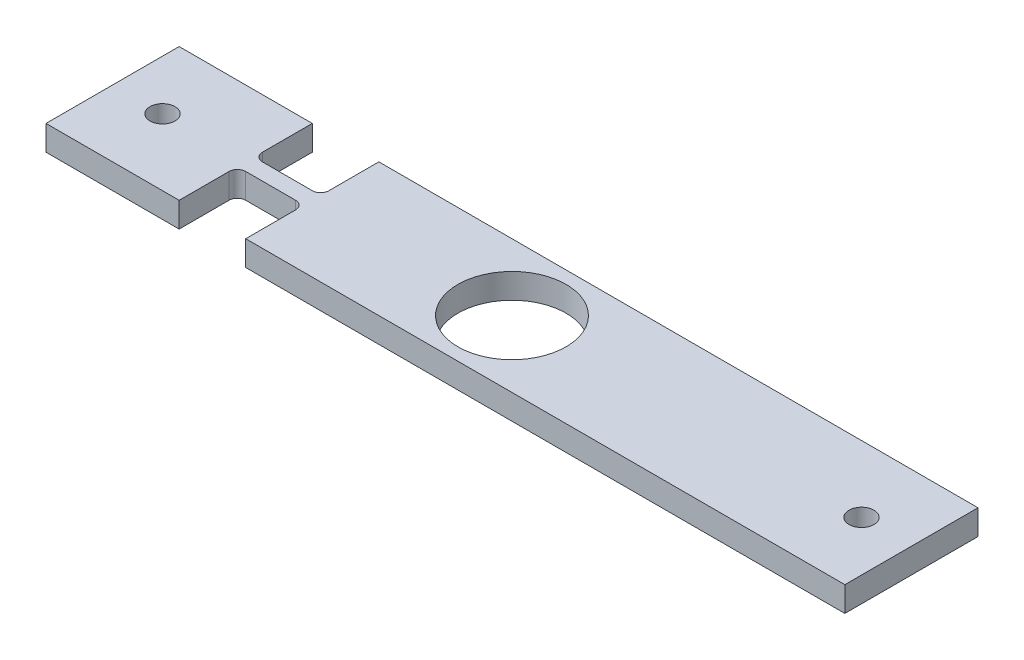
SolidWorks part; units mm, degrees
material "6061-T6 (SS)"
ref_plane "Front Plane" through (0, 0, 0) normal (0, 0, 1) x (1, 0, 0)
ref_plane "Top Plane" through (0, 0, 0) normal (0, 1, 0) x (1, 0, 0)
ref_plane "Right Plane" through (0, 0, 0) normal (1, 0, 0) x (0, 0, -1)
sketch "Sketch1" plane through (0, 0, 0) normal (0, 1, 0) x (1, 0, 0)
  line L1 (-152.4, 25.4) -> (152.4, 25.4)
  line L2 (-152.4, 25.4) -> (-152.4, -25.4)
  line L3 (-152.4, -25.4) -> (152.4, -25.4)
  line L4 (152.4, 25.4) -> (152.4, -25.4)
  line L5 (-152.4, 25.4) -> (152.4, -25.4) construction
  line L6 (-152.4, -25.4) -> (152.4, 25.4) construction
  point P0 (0, 0)
  dimension "D1" = 50.8
  dimension "D2" = 304.8
extrude "Boss-Extrude1" add sketch "Sketch1" along normal blind 9.525
sketch "Sketch2" plane through (0, 9.525, 0) normal (0, 1, 0) x (1, 0, 0)
  circle A0 centre (0, 0) radius 20.6375
  dimension "D1" = 41.275
extrude "Cut-Extrude1" cut sketch "Sketch2" against normal through all
sketch "Sketch3" plane through (0, 9.525, 0) normal (0, 1, 0) x (1, 0, 0)
  line L0 (152.4, -25.4) -> (152.4, 25.4) construction
  circle A0 centre (133.35, 0) radius 4.7625
  point P4 (0, 0)
  dimension "D1" = 9.525
  dimension "D2" = 19.05
extrude "Cut-Extrude2" cut sketch "Sketch3" against normal through all
sketch "Sketch4" plane through (0, 9.525, 0) normal (0, 1, 0) x (1, 0, 0)
  line L0 (152.4, 25.4) -> (-152.4, 25.4) construction
  line L1 (-101.6, 25.4) -> (-76.2, 25.4)
  line L2 (-101.6, 25.4) -> (-101.6, 6.35)
  line L3 (-98.425, 3.175) -> (-79.375, 3.175)
  line L4 (-76.2, 25.4) -> (-76.2, 6.35)
  line L5 (-101.6, -25.4) -> (-76.2, -25.4)
  line L6 (-101.6, -25.4) -> (-101.6, -6.35)
  line L7 (-98.425, -3.175) -> (-79.375, -3.175)
  line L8 (-76.2, -25.4) -> (-76.2, -6.35)
  line L9 (-152.4, -25.4) -> (152.4, -25.4) construction
  line L10 (-152.4, 25.4) -> (-152.4, -25.4) construction
  arc A0 (-101.6, -6.35) -> (-98.425, -3.175) centre (-98.425, -6.35) cw
  arc A1 (-79.375, -3.175) -> (-76.2, -6.35) centre (-79.375, -6.35) cw
  arc A2 (-79.375, 3.175) -> (-76.2, 6.35) centre (-79.375, 6.35) ccw
  arc A3 (-101.6, 6.35) -> (-98.425, 3.175) centre (-98.425, 6.35) ccw
  dimension "D4" = 3.175
  dimension "D1" = 6.35
  dimension "D2" = 50.8
  dimension "D3" = 25.4
extrude "Cut-Extrude3" cut sketch "Sketch4" against normal through all
sketch "Sketch5" plane through (0, 9.525, 0) normal (0, 1, 0) x (1, 0, 0)
  line L0 (-152.4, 25.4) -> (-152.4, -25.4) construction
  circle A0 centre (-133.35, 0) radius 4.7625
  point P4 (0, 0)
  dimension "D1" = 9.525
  dimension "D2" = 19.05
extrude "Cut-Extrude4" cut sketch "Sketch5" against normal through all
